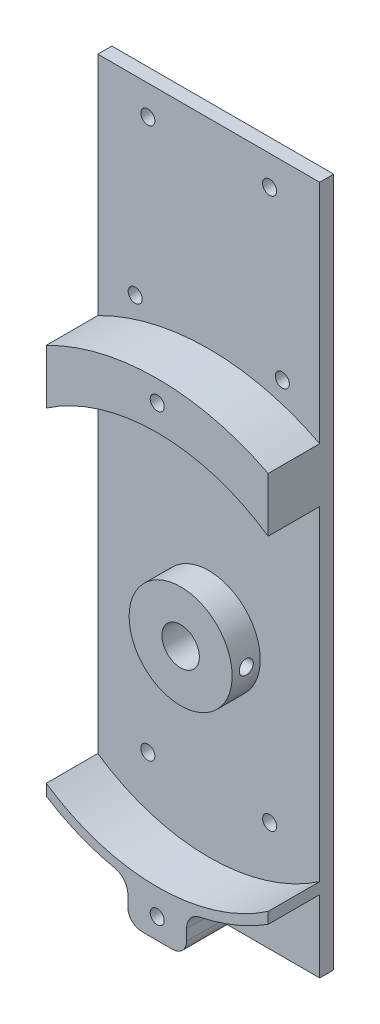
SolidWorks part; units mm, degrees
ref_plane "Front Plane" through (0, 0, 0) normal (0, 0, 1) x (1, 0, 0)
ref_plane "Top Plane" through (0, 0, 0) normal (0, 1, 0) x (1, 0, 0)
ref_plane "Right Plane" through (0, 0, 0) normal (1, 0, 0) x (0, 0, -1)
sketch "Sketch1" plane through (0, 0, 0) normal (0, 1, 0) x (1, 0, 0)
  line L0 (0, 0) -> (10, 0)
  line L1 (10, 0) -> (10, -40)
  line L2 (0, 0) -> (-10, 0)
  line L3 (-10, 0) -> (-10, -40)
  line L4 (-10, -40) -> (10, -40)
  line L5 (0, -46.4243) -> (0, 6.4077) construction
  line L6 (-14.7387, 0) -> (-23.7006, -94.809)
  line L7 (-9.906, -20.0083) -> (9.906, -20.0083) construction
  line L8 (0, -46.4243) -> (0, -94.809) construction
  line L9 (-23.7006, -94.809) -> (0, -94.809) construction
  line L21 (0, 6.4077) -> (0, 0) construction
  line L22 (-9.906, -9.7213) -> (9.906, -9.7213) construction
  line L23 (14.7387, 0) -> (-14.7387, 0) construction
  line L24 (14.7387, 0) -> (23.6804, -94.809)
  line L25 (-23.7006, -94.809) -> (23.6804, -94.809) construction
  line L26 (-23.7006, -94.809) -> (23.6804, -94.809)
  line L27 (-23.7006, -94.809) -> (-23.7006, -97.809)
  line L28 (-23.7006, -97.809) -> (23.6804, -97.809)
  line L29 (23.6804, -97.809) -> (23.6804, -94.809)
  circle A0 centre (-5.08, -43.7573) radius 2.1844
  arc A1 (-6.5248, -45.3956) -> (-3.6352, -45.3956) centre (-5.08, -43.7573) cw
  circle A2 centre (5.08, -43.7573) radius 2.1844
  arc A4 (-14.7387, 0) -> (14.7387, 0) centre (0, -1.5364) cw
  circle A5 centre (5.08, 3.7407) radius 2.1844
  circle A6 centre (-5.08, 3.7407) radius 2.1844
  point P37 (0, 0)
extrude "Boss-Extrude2" add sketch "Sketch1" against normal blind 115 and the other way blind 32.1335 contours L28 L29 L26 L27 region at (-0.0101, 0, 96.309)
sketch "Sketch3" plane through (0, 0, 94.809) normal (0, 0, -1) x (-1, 0, 0)
  line L0 (-12.9899, -91.5965) -> (13.0101, -91.5965) construction
  line L1 (0.0101, -62.5) -> (-7.9899, -62.5) construction
  line L2 (0.0101, -32.8665) -> (23.7006, -32.8665) construction
  line L3 (0.0101, -91.5965) -> (0.0101, -97.8665) construction
  line L4 (23.7006, -125) -> (23.7006, 0) construction
  line L5 (0.0101, -62.5) -> (4.0101, -55.5718) construction
  line L6 (0.0101, -62.5) -> (4.0101, -69.4282) construction
  line L7 (-23.6804, 32.1335) -> (23.7006, 32.1335) construction
  line L8 (-23.6804, -97.8665) -> (23.7006, -97.8665) construction
  line L9 (0.0101, 25.8635) -> (0.0101, 32.1335) construction
  line L10 (-12.9899, 25.8635) -> (13.0101, 25.8635) construction
  line L11 (0.0101, -97.8665) -> (0.0101, -92.8665) construction
  line L12 (0.0101, 32.1335) -> (-23.6804, 32.1335) construction
  circle A0 centre (-12.9899, -91.5965) radius 1.5
  circle A1 centre (0.0101, -62.5) radius 4
  circle A2 centre (13.0101, -91.5965) radius 1.5
  circle A4 centre (-15.6902, -8.4173) radius 1.5
  circle A5 centre (15.7135, -8.4475) radius 1.5
  circle A6 centre (0.0101, -62.5) radius 11
  circle A7 centre (13.0101, 25.8635) radius 1.5
  circle A8 centre (-12.9899, 25.8635) radius 1.5
  point P16 (0.0101, -62.5)
  point P19 (0.0101, -62.5)
  point P22 (0.0101, -62.5)
  dimension "D1" = 3
extrude "Cut-Extrude1" cut sketch "Sketch3" against normal blind 10 contours A1 | A0 | A7 | A8 | A5 | A4 | A2 region at (12.9899, -91.5965, 94.809) region at (-0.0101, -62.5, 94.809) region at (15.6902, -8.4173, 94.809) region at (-15.7135, -8.4475, 94.809) region at (-13.0101, 25.8635, 94.809) region at (12.9899, 25.8635, 94.809)
sketch "Sketch4" plane through (0, 0, 97.809) normal (0, 0, 1) x (1, 0, 0)
  line L0 (23.6804, -99.5778) -> (23.6804, -97.1809)
  line L1 (-23.7006, -99.5778) -> (-23.7006, -97.1809)
  line L2 (-23.7006, -25.4222) -> (-23.7006, -27.8191)
  line L3 (23.6804, -25.4222) -> (23.6804, -27.8191)
  line L4 (-0.0101, -62.5) -> (-0.0101, -108.5) construction
  line L5 (-0.0101, -110) -> (-0.0101, -108.5) construction
  line L6 (6.2632, -109.027) -> (6.2632, -111.4141)
  line L7 (3.2632, -114.4141) -> (-3.2834, -114.4141)
  line L8 (-6.2834, -109.027) -> (-6.2834, -111.4141)
  line L9 (-0.0101, -62.5) -> (12.8534, -62.5) construction
  line L10 (-0.0101, -10.5) -> (0, 0) construction
  circle A0 centre (-0.0101, -62.5) radius 42
  circle A1 centre (-0.0101, -62.5) radius 44
  circle A2 centre (-0.0101, -110) radius 1.5
  arc A3 (6.2632, -111.4141) -> (3.2632, -114.4141) centre (3.2632, -111.4141) cw
  arc A4 (6.2632, -109.027) -> (8.6929, -105.6307) centre (9.8167, -109.0019) cw
  arc A5 (-6.2834, -111.4141) -> (-3.2834, -114.4141) centre (-3.2834, -111.4141) ccw
  arc A6 (-6.2834, -109.027) -> (-8.7131, -105.6307) centre (-9.8369, -109.0019) ccw
  circle A7 centre (-0.0101, -15) radius 1.5
  circle A8 centre (-15.7104, -8.9173) radius 1.5
  circle A9 centre (15.6932, -8.9475) radius 1.5
  circle A12 centre (-0.0101, -62.5) radius 5
  circle A13 centre (-0.0101, -62.5) radius 52
  line M6 (23.6804, -115) -> (23.6804, 32.1335)
  line M8 (-23.7006, 32.1335) -> (-23.7006, -115)
  dimension "D1" = 3
extrude "Boss-Extrude6" add sketch "Sketch4" along normal blind 11 contours A1 A0 M8 M6 | A1 A0 M6 M8 | A6 L8 L7 L6 A4 A1 A2 | A1 A7 region at (16.2861, -102.8506, 97.809) region at (6.768, -106.8209, 97.809) region at (-0.0101, -20.0171, 97.809) region at (-0.0101, -16.6517, 97.809)
extrude "Cut-Extrude2" cut sketch "Sketch4<3>" against normal blind 10 contours A2 | A7 region at (-0.0101, -110, 97.809) region at (-0.0101, -15, 97.809)
sketch "Sketch4<3>" plane through (0, 0, 97.809) normal (0, 0, 1) x (1, 0, 0) same geometry as "Sketch4"
extrude "Boss-Extrude7" add sketch "Sketch3<5>" against normal blind 9 contours A6 A1 region at (10.6788, -62.5, 94.809)
sketch "Sketch3<5>" plane through (0, 0, 94.809) normal (0, 0, -1) x (-1, 0, 0) same geometry as "Sketch3"
ref_plane "Plane2" through (10.9899, 0, 0) normal (1, 0, 0) x (0, 0, -1)
sketch "Sketch8" plane through (10.9899, 0, 0) normal (1, 0, 0) x (0, 0, -1)
  line L0 (-103.7761, -62.3968) -> (-97.7863, -62.3968) construction
  circle A0 centre (-100.7812, -62.3968) radius 1.5
extrude "Cut-Extrude3" cut sketch "Sketch8" against normal blind 9
equation "\".5mmmm\"=1"
